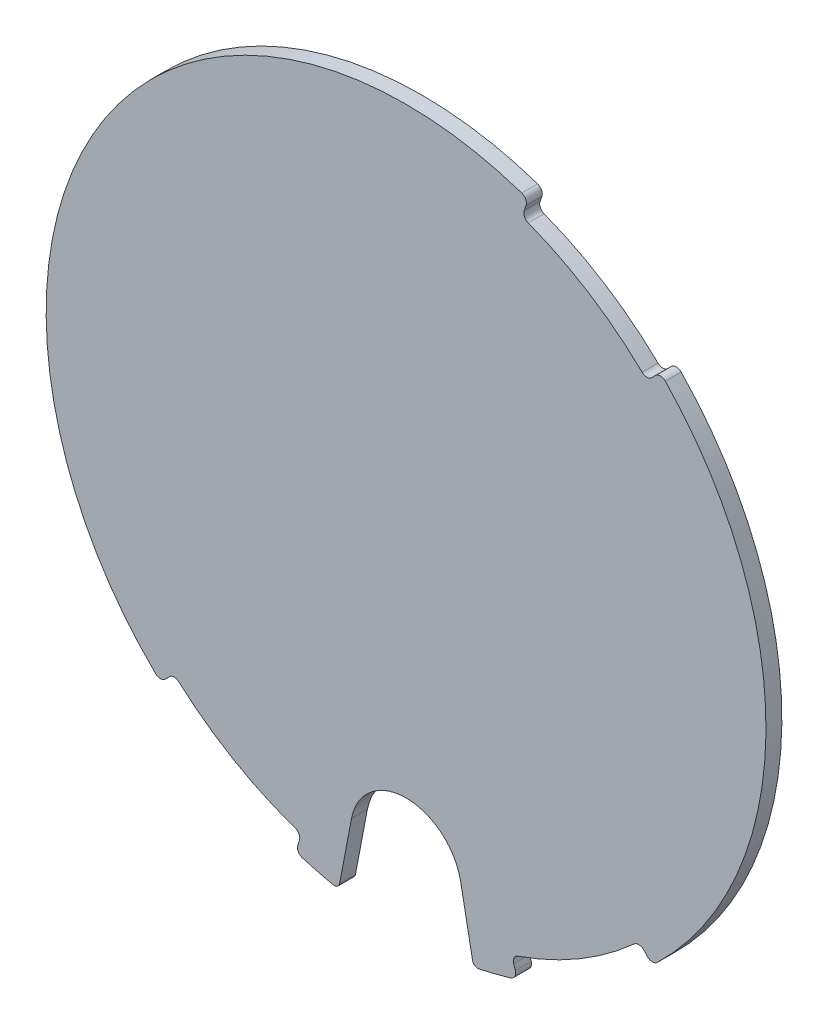
SolidWorks part; units mm, degrees
ref_plane "Alzado" through (0, 0, 0) normal (0, 0, 1) x (1, 0, 0)
ref_plane "Planta" through (0, 0, 0) normal (0, 1, 0) x (1, 0, 0)
ref_plane "Vista lateral" through (0, 0, 0) normal (1, 0, 0) x (0, 0, -1)
sketch "Model" plane through (0, 0, 0) normal (0, 0, 1) x (1, 0, 0)
  line L12 (23.9841, 23.7015) -> (20.8347, 18.3355)
  line L13 (20.8347, 18.3355) -> (9.1701, 24.9845)
  line L14 (9.1701, 24.9845) -> (11.9696, 30.4675)
  line L15 (11.9696, 30.4675) -> (23.9841, 23.7015)
  line L16 (23.5645, -22.1803) -> (11.6405, -29.0235)
  line L17 (11.6405, -29.0235) -> (8.6335, -23.7355)
  line L18 (8.6335, -23.7355) -> (20.4535, -16.8923)
  line L19 (20.4535, -16.8923) -> (23.5645, -22.1803)
  line L20 (-5.4405, -24.0979) -> (-8.4734, -29.4636)
  line L21 (-8.4734, -29.4636) -> (-20.5268, -22.4648)
  line L22 (-20.5268, -22.4648) -> (-17.5718, -17.1768)
  line L23 (-17.5718, -17.1768) -> (-5.4405, -24.0979)
  line L24 (6.9505, -26.589) -> (6.7665, -25.2108)
  line L25 (6.7665, -25.2108) -> (6.2386, -23.9493)
  line L26 (6.2386, -23.9493) -> (5.403, -22.8668)
  line L27 (5.403, -22.8668) -> (4.2959, -22.0254)
  line L28 (4.2959, -22.0254) -> (3.0068, -21.5041)
  line L29 (3.0068, -21.5041) -> (1.6493, -21.3393)
  line L30 (1.6493, -21.3393) -> (0.2952, -21.5305)
  line L31 (0.2952, -21.5305) -> (-0.9834, -22.077)
  line L32 (-0.9834, -22.077) -> (-2.0739, -22.9397)
  line L33 (-2.0739, -22.9397) -> (-2.8882, -24.0384)
  line L34 (-2.8882, -24.0384) -> (-3.3914, -25.31)
  line L35 (-3.3914, -25.31) -> (-3.5485, -26.6915)
  line L36 (-4.4685, -32.0246) -> (-3.5485, -26.6915)
  line L37 (7.8915, -32.0205) -> (11.0678, -31.275)
  line L38 (11.0678, -31.275) -> (14.108, -30.2492)
  line L39 (14.108, -30.2492) -> (16.9999, -28.9593)
  line L40 (16.9999, -28.9593) -> (19.7314, -27.4213)
  line L41 (19.7314, -27.4213) -> (22.2902, -25.6513)
  line L42 (22.2902, -25.6513) -> (24.6641, -23.6655)
  line L43 (24.6641, -23.6655) -> (26.841, -21.4799)
  line L44 (26.841, -21.4799) -> (28.8088, -19.1106)
  line L45 (28.8088, -19.1106) -> (30.5551, -16.5737)
  line L46 (30.5551, -16.5737) -> (32.0679, -13.8853)
  line L47 (32.0679, -13.8853) -> (33.3349, -11.0616)
  line L48 (33.3349, -11.0616) -> (34.344, -8.1185)
  line L49 (34.344, -8.1185) -> (35.083, -5.0721)
  line L50 (35.083, -5.0721) -> (35.5397, -1.9387)
  line L51 (35.5397, -1.9387) -> (35.702, 1.2658)
  line L52 (35.702, 1.2658) -> (35.5575, 4.5252)
  line L53 (35.5575, 4.5252) -> (35.105, 7.7563)
  line L54 (35.105, 7.7563) -> (34.3609, 10.8774)
  line L55 (34.3609, 10.8774) -> (33.3403, 13.875)
  line L56 (33.3403, 13.875) -> (32.058, 16.7354)
  line L57 (32.058, 16.7354) -> (30.5289, 19.445)
  line L58 (30.5289, 19.445) -> (28.7681, 21.9903)
  line L59 (28.7681, 21.9903) -> (26.7902, 24.3576)
  line L60 (26.7902, 24.3576) -> (24.6104, 26.5334)
  line L61 (24.6104, 26.5334) -> (22.2435, 28.504)
  line L62 (22.2435, 28.504) -> (19.7044, 30.2558)
  line L63 (19.7044, 30.2558) -> (17.008, 31.7752)
  line L64 (17.008, 31.7752) -> (14.1693, 33.0487)
  line L65 (14.1693, 33.0487) -> (11.2032, 34.0627)
  line L66 (11.2032, 34.0627) -> (8.1245, 34.8034)
  line L67 (8.1245, 34.8034) -> (4.9482, 35.2574)
  line L68 (4.9482, 35.2574) -> (1.6892, 35.411)
  line L69 (1.6892, 35.411) -> (-1.5698, 35.2552)
  line L70 (-1.5698, 35.2552) -> (-4.7458, 34.7991)
  line L71 (-4.7458, 34.7991) -> (-7.824, 34.0563)
  line L72 (-7.824, 34.0563) -> (-10.7894, 33.0405)
  line L73 (-10.7894, 33.0405) -> (-13.6273, 31.7651)
  line L74 (-13.6273, 31.7651) -> (-16.3227, 30.2438)
  line L75 (-16.3227, 30.2438) -> (-18.8606, 28.4903)
  line L76 (-18.8606, 28.4903) -> (-21.2262, 26.5182)
  line L77 (-21.2262, 26.5182) -> (-23.4046, 24.341)
  line L78 (-23.4046, 24.341) -> (-25.3808, 21.9723)
  line L79 (-25.3808, 21.9723) -> (-27.14, 19.4259)
  line L80 (-27.14, 19.4259) -> (-28.6673, 16.7153)
  line L81 (-28.6673, 16.7153) -> (-29.9477, 13.854)
  line L82 (-29.9477, 13.854) -> (-30.9663, 10.8558)
  line L83 (-30.9663, 10.8558) -> (-31.7083, 7.7341)
  line L84 (-31.7083, 7.7341) -> (-32.1587, 4.5028)
  line L85 (-32.1587, 4.5028) -> (-32.301, 1.2432)
  line L86 (-32.301, 1.2432) -> (-32.1366, -1.9611)
  line L87 (-32.1366, -1.9611) -> (-31.6779, -5.0943)
  line L88 (-31.6779, -5.0943) -> (-30.9369, -8.1401)
  line L89 (-30.9369, -8.1401) -> (-29.9258, -11.0825)
  line L90 (-29.9258, -11.0825) -> (-28.6569, -13.9055)
  line L91 (-28.6569, -13.9055) -> (-27.1423, -16.5929)
  line L92 (-27.1423, -16.5929) -> (-25.3943, -19.1286)
  line L93 (-25.3943, -19.1286) -> (-23.425, -21.4966)
  line L94 (-23.425, -21.4966) -> (-21.2466, -23.6807)
  line L95 (-21.2466, -23.6807) -> (-18.8713, -25.665)
  line L96 (-18.8713, -25.665) -> (-16.3114, -27.4332)
  line L97 (-16.3114, -27.4332) -> (-13.5789, -28.9694)
  line L98 (-13.5789, -28.9694) -> (-10.6861, -30.2574)
  line L99 (-10.6861, -30.2574) -> (-7.6453, -31.2812)
  line L100 (-7.6453, -31.2812) -> (-4.4685, -32.0246)
  line L101 (6.9505, -26.589) -> (7.8915, -32.0205)
  point P1 (-4.4685, -32.0246)
  point P2 (-10.7894, 33.0405)
sketch "Croquis3" plane through (0, 0, 0) normal (0, 0, 1) x (1, 0, 0)
  line L0 (-19.3008, -18.5746) -> (-7.1406, -25.5122) construction
  line L1 (-19.3008, -18.5746) -> (-22.3732, -23.9598) construction
  line L2 (-7.1406, -25.5122) -> (-10.213, -30.8974) construction
  line L3 (-22.3732, -23.9598) -> (-10.213, -30.8974) construction
  line L4 (6.9334, -25.1498) -> (19.0493, -18.1352) construction
  line L5 (6.9334, -25.1498) -> (10.0398, -30.5154) construction
  line L6 (19.0493, -18.1352) -> (22.1558, -23.5009) construction
  line L7 (10.0398, -30.5154) -> (22.1558, -23.5009) construction
  line L8 (10.2361, 28.9943) -> (22.4348, 22.1246) construction
  line L9 (10.2361, 28.9943) -> (7.1938, 23.592) construction
  line L10 (22.4348, 22.1246) -> (19.3925, 16.7223) construction
  line L11 (7.1938, 23.592) -> (19.3925, 16.7223) construction
  line L12 (0, 0) -> (0, -28.0037) construction
  line L13 (0, 0) -> (-6.3752, -33.4001) construction
  line L14 (-5.1573, -27.0193) -> (-6.2808, -32.9053)
  line L15 (5.1573, -27.0193) -> (6.2808, -32.9053)
  line L31 (7.4092, 23.4707) -> (7.7711, 24.617) construction
  circle A0 centre (0, 0) radius 34.0031 construction
  circle A1 centre (0, -28.0037) radius 5.2504 construction
  arc A2 (-5.1573, -27.0193) -> (5.1573, -27.0193) centre (0, -28.0037) cw
  arc A3 (-6.873, -33.3012) -> (6.873, -33.3012) centre (0, 0) cw
  arc A5 (-6.2808, -32.9053) -> (-6.873, -33.3012) centre (-6.7719, -32.8115) cw
  arc A6 (6.2808, -32.9053) -> (6.873, -33.3012) centre (6.7719, -32.8115) ccw
  point P0 (-5.1573, -27.0193)
  dimension "D13" = 68.0062
  dimension "D14" = 10.5008
  dimension "D16" = 0.5
  dimension "D1" = 28.0037
  dimension "D2" = 6.2
  dimension "D3" = 14
  dimension "D4" = 18.5746
  dimension "D5" = 18.1352
  dimension "D6" = 16.7223
  dimension "D7" = 23.592
  dimension "D8" = 25.5122
  dimension "D9" = 25.1498
  dimension "D10" = 7.1938
  dimension "D11" = 6.9334
  dimension "D12" = 7.1406
extrude "Saliente-Extruir2" add sketch "Croquis3" along normal blind 1.5
sketch "Croquis5" [suppressed] plane through (0, 0, 0) normal (0, 0, 1) x (1, 0, 0)
  circle A0 centre (0, -28.0037) radius 5.2504 construction
  circle A1 centre (0, 0) radius 34.0031 construction
  circle A2 centre (0, -28.0037) radius 5.2504 construction
  circle A3 centre (0, 0) radius 34.0031
  circle A4 centre (0, -28.0037) radius 3.25
  dimension "D1" = 6.5
extrude "Saliente-Extruir3" [suppressed] add sketch "Croquis5" along normal blind 1.5 contours A3 | A4
sketch "Croquis4" plane through (0, 0, 0) normal (0, 0, 1) x (1, 0, 0)
  line L0 (10.2361, 28.9943) -> (22.4348, 22.1246) construction
  line L1 (22.4348, 22.1246) -> (19.3925, 16.7223) construction
  line L2 (7.1938, 23.592) -> (19.3925, 16.7223) construction
  line L3 (10.2361, 28.9943) -> (7.1938, 23.592) construction
  line L4 (10.2361, 28.9943) -> (22.4348, 22.1246) construction
  line L5 (22.4348, 22.1246) -> (19.3925, 16.7223) construction
  line L6 (7.1938, 23.592) -> (19.3925, 16.7223) construction
  line L7 (10.2361, 28.9943) -> (7.1938, 23.592) construction
  line L24 (0, 0) -> (17.263, 27.1851) construction
  line L26 (22.7594, 22.7826) -> (24.0316, 24.056)
  line L27 (10.941, 30.2875) -> (11.5525, 31.9804)
  arc A0 (6.873, -33.3012) -> (-6.873, -33.3012) centre (0, 0) ccw construction
  arc A1 (24.0316, 24.056) -> (11.5525, 31.9804) centre (0, 0) ccw
  arc A2 (10.941, 30.2875) -> (22.7594, 22.7826) centre (0, 0) cw
  point P14 (16.0978, -27.0081)
  point P19 (17.263, 27.1851)
  dimension "D4" = 34.0031
  dimension "D1" = 14
  dimension "D3" = 1.8
  dimension "D2" = 32.2031
extrude "Cortar-Extruir6" cut sketch "Croquis4" along normal blind 1.5
fillet "Redondeo2" radius 0.65 4 edges at (11.5525, 31.9804, 0.75) (24.0316, 24.056, 0.75) (22.7594, 22.7826, 0.75) (10.941, 30.2875, 0.75)
ref_axis "Eje1" through (0, 0, -0.075) along (0, 0, 1)
pattern_circular "MatrizC2" count 2 every 182 about axis through (0, 0, -0.075) along (0, 0, 1) of "Cortar-Extruir6", "Redondeo2"
pattern_circular "MatrizC3" count 2 every 243 about axis through (0, 0, -0.075) along (0, 0, 1) of "Redondeo2", "Cortar-Extruir6"
sketch "Croquis6" [suppressed] plane through (0, 0, 1.5) normal (0, 0, 1) x (1, 0, 0)
  line L0 (0, 0) -> (-19.9865, 27.5091) construction
  line L1 (-24.1372, 21.3128) -> (-25.4888, 22.5063)
  line L2 (-12.8109, 29.5418) -> (-13.5283, 31.1961)
  line L3 (0, 0) -> (0, 35.0983) construction
  line L5 (11.1596, 30.8928) -> (11.3295, 31.3631)
  line L6 (23.5677, 23.5917) -> (23.2143, 23.2379)
  arc A0 (10.9271, 32.1995) -> (24.4958, 23.5831) centre (0, 0) ccw construction
  arc A1 (-24.1372, 21.3128) -> (-12.8109, 29.5418) centre (0, 0) cw
  arc A9 (11.3295, 31.3631) -> (10.9271, 32.1995) centre (10.7182, 31.584) ccw
  arc A10 (10.9271, 32.1995) -> (24.4958, 23.5831) centre (0, 0) ccw
  arc A11 (24.4958, 23.5831) -> (23.5677, 23.5917) centre (24.0276, 23.1323) ccw
  arc A12 (22.3042, 23.2284) -> (23.2143, 23.2379) centre (22.7544, 23.6973) ccw
  arc A13 (22.3042, 23.2284) -> (11.5381, 30.0651) centre (0, 0) ccw
  arc A14 (11.1596, 30.8928) -> (11.5381, 30.0651) centre (11.771, 30.672) ccw
  arc A16 (-13.5283, 31.1961) -> (-25.4888, 22.5063) centre (0, 0) ccw
  point P16 (-18.9267, 26.0503)
  dimension "D1" = 0
  dimension "D4" = 32.2
  dimension "D2" = 14
  dimension "D3" = 36
extrude "Cortar-Extruir7" [suppressed] cut sketch "Croquis6" against normal blind 1.5
fillet "Redondeo3" [suppressed] radius 0.65
sketch "Croquis7" [suppressed] plane through (0, 0, 1.5) normal (0, 0, 1) x (1, 0, 0)
  line L0 (0, 0) -> (-13.2861, -31.3) construction
  line L1 (-13.9886, -30.9924) -> (-13.6766, -30.3011)
  line L2 (-13.6766, -30.3011) -> (0, 0) construction
  line L3 (-12.5767, -31.5917) -> (-12.2962, -30.887)
  line L4 (0, 0) -> (0, -34.0031) construction
  arc A0 (-25.9225, 22.0053) -> (24.4958, 23.5831) centre (0, 0) ccw construction
  arc A1 (-12.2962, -30.887) -> (-13.6766, -30.3011) centre (-12.993, -30.6096) ccw
  arc A2 (-12.5767, -31.5917) -> (-13.9886, -30.9924) centre (0, 0) cw
  arc M12 (-25.9225, 22.0053) -> (24.4958, 23.5831) centre (0, 0) ccw
  dimension "D1" = 1.5
  dimension "D2" = 0.75
  dimension "D3" = 23
extrude "Cortar-Extruir8" [suppressed] cut sketch "Croquis7" against normal blind 1.5 contours L3 A1 L1 M12
fillet "Redondeo4" [suppressed] radius 0.65
equation "\"D2@Croquis4\"=\"D4@Croquis4\"-1.8"
equation "\"D2@Croquis7\"=\"D1@Croquis7\"/2"
